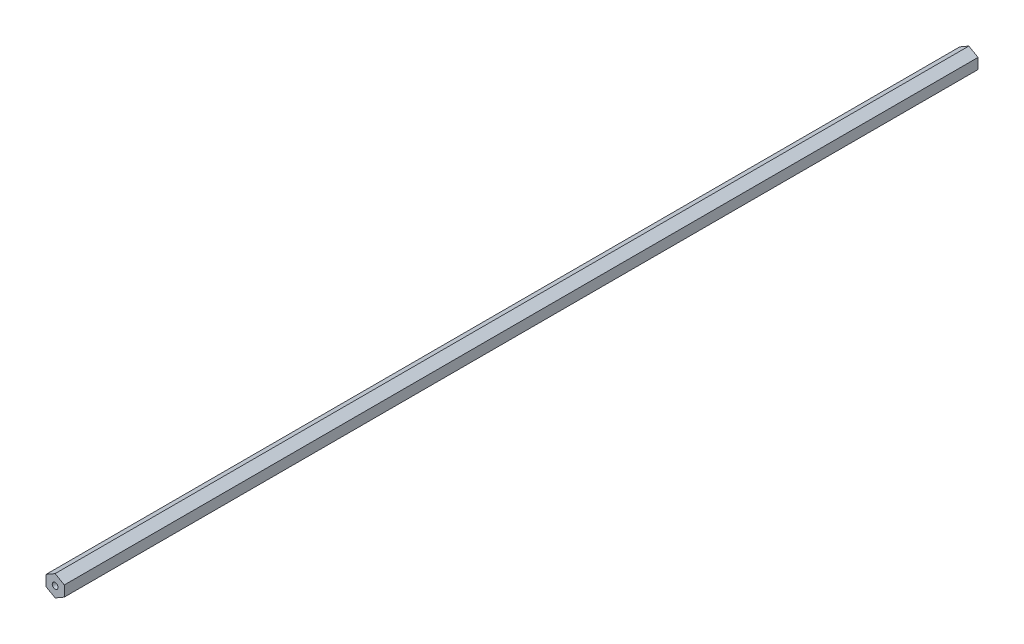
SolidWorks part; units mm, degrees
ref_plane "Front Plane" through (0, 0, 0) normal (0, 0, 1) x (1, 0, 0)
ref_plane "Top Plane" through (0, 0, 0) normal (0, 1, 0) x (1, 0, 0)
ref_plane "Right Plane" through (0, 0, 0) normal (1, 0, 0) x (0, 0, -1)
sketch "Sketch1" plane through (0, 0, 0) normal (0, 0, 1) x (1, 0, 0)
  line L1 (6.35, -3.6662) -> (6.35, 3.6662)
  line L2 (6.35, 3.6662) -> (0, 7.3323)
  line L3 (0, 7.3323) -> (-6.35, 3.6662)
  line L4 (-6.35, 3.6662) -> (-6.35, -3.6662)
  line L5 (-6.35, -3.6662) -> (0, -7.3323)
  line L6 (0, -7.3323) -> (6.35, -3.6662)
  circle A0 centre (0, 0) radius 6.35 construction
  dimension "D1" = 12.7
extrude "Boss-Extrude1" add sketch "Sketch1" along normal mid plane 635
sketch "Sketch2" plane through (0, 0, 317.5) normal (0, 0, 1) x (1, 0, 0)
  circle A0 centre (0, 0) radius 2.4892
  dimension "D1" = 4.9784
hole_wizard "#10-32 Tapped Hole1" positions "3DSketch1" profile "Sketch3" tap size "#10-32" standard "ANSI Inch"
sketch3d "3DSketch1"
  line L1 (-6.35, 3.6662, -317.5) -> (-6.35, -3.6662, -317.5) construction
  point P0 (0, 0, 317.5)
  point P3 (0, 0, -317.5)
  point P13 (-6.35, 0, -317.5)
sketch "Sketch3" plane through (0, 0, 317.5) normal (1, 0, 0) x (0, -1, 0)
  line L0 (0, 0) -> (0, 17.5608)
  line L1 (0, 17.5608) -> (2.0193, 16.3474)
  line L2 (2.0193, 16.3474) -> (2.0193, 0)
  line L5 (2.0193, 0) -> (0, 0)
  line L10 (0, 17.5608) -> (-2.0193, 16.3474) construction
  line L11 (0, -6.35) -> (0, 107.95) construction
  dimension "Tap Drill Dia." = 4.0386
  dimension "Tap Drill Depth" = 16.3474
  dimension "Drill Angle" = 118
cosmetic thread "Hole Thread1" parameters "D1"=13.97, "D2"=4.826
cosmetic thread "Hole Thread2" parameters "D1"=13.97, "D2"=4.826
